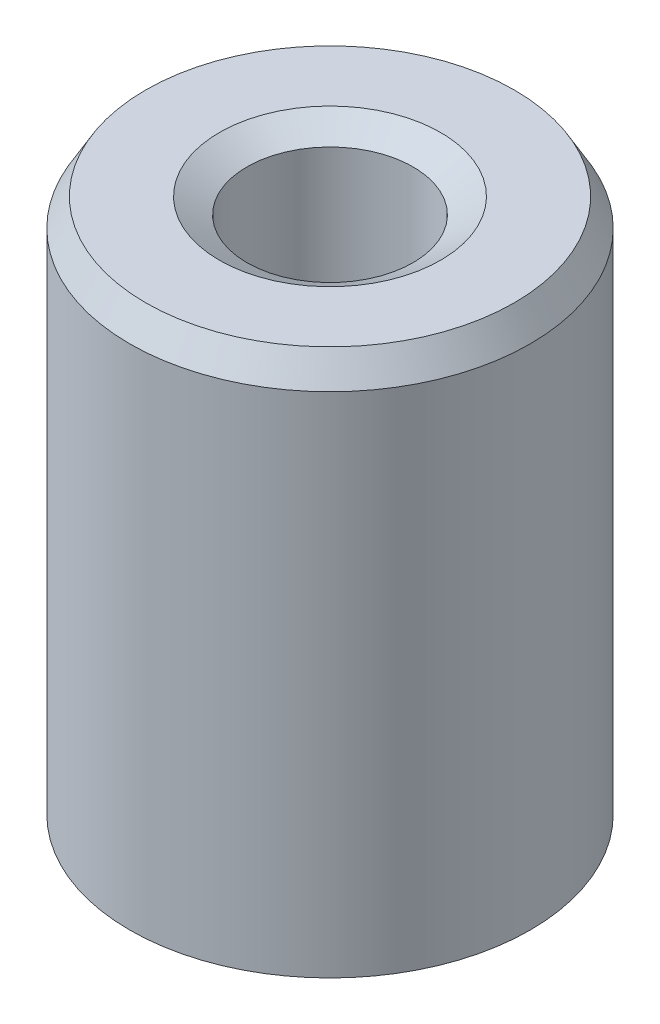
SolidWorks part; units mm, degrees
ref_plane "Front Plane" through (0, 0, 0) normal (0, 0, 1) x (1, 0, 0)
ref_plane "Top Plane" through (0, 0, 0) normal (0, 1, 0) x (1, 0, 0)
ref_plane "Right Plane" through (0, 0, 0) normal (1, 0, 0) x (0, 0, -1)
sketch "Sketch1" plane through (0, 0, 0) normal (0, 1, 0) x (1, 0, 0)
  circle A0 centre (0, 0) radius 22.5
  dimension "SLEEVE_OD" = 45
extrude "Boss-Extrude1" add sketch "Sketch1" along normal blind 61.9346
sketch "Sketch2" plane through (0, 0, 0) normal (0, 1, 0) x (1, 0, 0)
  circle A0 centre (0, 0) radius 9.3318
  dimension "BORE_D" = 18.6635
extrude "Cut-Extrude1" cut sketch "Sketch2" along normal through all
chamfer "Chamfer1" distance 3.1011 angle 30 4 edges at (0, 61.9346, 9.3318) (0, 0, 9.3318) (0, 0, 22.5) (0, 61.9346, 22.5) first distance on face at (0, 61.9346, 9.3318) first distance on face at (0, 0, 9.3318) first distance on face at (0, 61.9346, 22.5)
